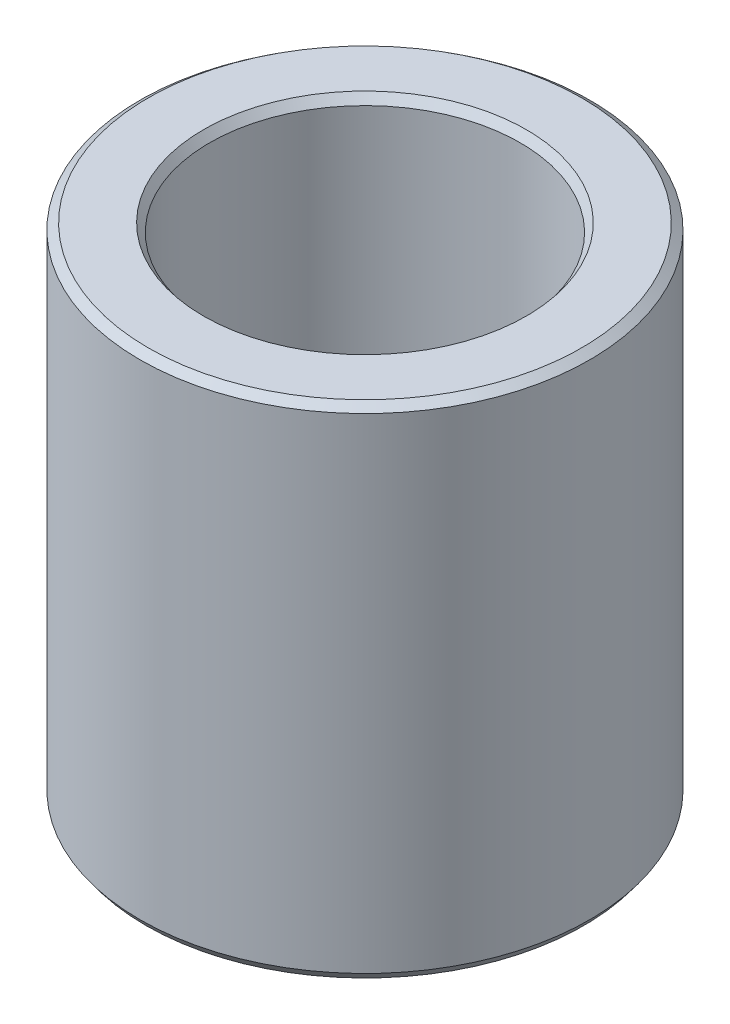
SolidWorks part; units mm, degrees
ref_plane "Front Plane" through (0, 0, 0) normal (0, 0, 1) x (1, 0, 0)
ref_plane "Top Plane" through (0, 0, 0) normal (0, 1, 0) x (1, 0, 0)
ref_plane "Right Plane" through (0, 0, 0) normal (1, 0, 0) x (0, 0, -1)
sketch "Sketch1" plane through (0, 0, 0) normal (0, 1, 0) x (1, 0, 0)
  circle A0 centre (0, 0) radius 15
  dimension "SLEEVE_OD" = 30
extrude "Boss-Extrude1" add sketch "Sketch1" along normal blind 33.2994
sketch "Sketch2" plane through (0, 0, 0) normal (0, 1, 0) x (1, 0, 0)
  circle A0 centre (0, 0) radius 10.3591
  dimension "BORE_D" = 20.7181
extrude "Cut-Extrude1" cut sketch "Sketch2" along normal through all
chamfer "Chamfer1" distance 0.4096 angle 53.406 4 edges at (0, 33.2994, 10.3591) (0, 0, 10.3591) (0, 0, 15) (0, 33.2994, 15) first distance on face at (0, 33.2994, 10.3591) first distance on face at (0, 0, 10.3591) first distance on face at (0, 33.2994, 15)
